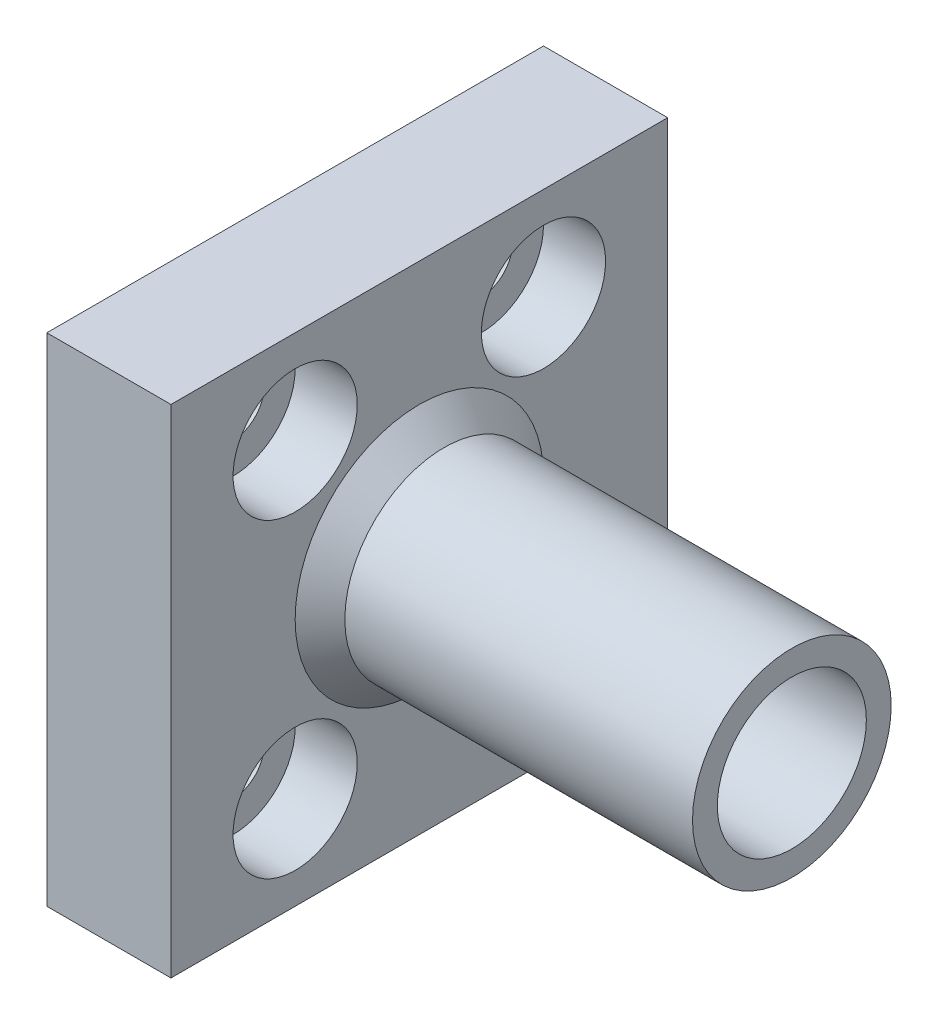
SolidWorks part; units mm, degrees
ref_plane "Front Plane" through (0, 0, 0) normal (0, 0, 1) x (1, 0, 0)
ref_plane "Top Plane" through (0, 0, 0) normal (0, 1, 0) x (1, 0, 0)
ref_plane "Right Plane" through (0, 0, 0) normal (1, 0, 0) x (0, 0, -1)
other "Configuration Table"
sketch "Sketch1" plane through (0, 0, 0) normal (1, 0, 0) x (0, 0, -1)
  line L1 (20, -20) -> (-20, -20)
  line L2 (20, -20) -> (20, 20)
  line L3 (20, 20) -> (-20, 20)
  line L4 (-20, -20) -> (-20, 20)
  line L5 (20, -20) -> (-20, 20) construction
  line L6 (20, 20) -> (-20, -20) construction
  point P0 (0, 0)
  dimension "D1" = 40
  dimension "D2" = 40
extrude "Boss-Extrude1" add sketch "Sketch1" along normal blind 10
sketch "Sketch2" plane through (10, 0, 0) normal (1, 0, 0) x (0, 0, -1)
  circle A0 centre (0, 0) radius 8
extrude "Boss-Extrude2" add sketch "Sketch2" along normal blind 30
sketch "Sketch3" plane through (10, 0, 0) normal (1, 0, 0) x (0, 0, -1)
  line L0 (-10, -20) -> (-10, 20) construction
  line L1 (-20, -20) -> (20, -20) construction
  line L2 (20, 20) -> (-20, 20) construction
  line L3 (10, -20) -> (10, 20) construction
  dimension "D1" = 10
  dimension "D2" = 10
sketch "Sketch4" plane through (10, 0, 0) normal (1, 0, 0) x (0, 0, -1)
  line L0 (-10, -20) -> (-10, 20) construction
  line L1 (10, -20) -> (10, 20) construction
  circle A0 centre (-10, 12.5) radius 2.5
  circle A1 centre (-10, -12.5) radius 2.5
  circle A2 centre (10, 12.5) radius 2.5
  circle A3 centre (10, -12.5) radius 2.5
  dimension "D1" = 12.5
  dimension "D2" = 12.5
extrude "Cut-Extrude1" cut sketch "Sketch4" against normal through all
sketch "Sketch5" plane through (40, 0, 0) normal (1, 0, 0) x (0, 0, -1)
  circle A0 centre (0, 0) radius 6
extrude "Cut-Extrude2" cut sketch "Sketch5" against normal blind 34
sketch "Sketch6" plane through (10, 0, 0) normal (1, 0, 0) x (0, 0, -1)
  circle A0 centre (-10, 12.5) radius 5
  circle A1 centre (10, 12.5) radius 5
  circle A2 centre (10, -12.5) radius 5
  circle A3 centre (-10, -12.5) radius 5
extrude "Cut-Extrude3" cut sketch "Sketch6" against normal blind 5
sketch "Sketch7" plane through (6, 0, 0) normal (1, 0, 0) x (0, 0, -1)
  circle A0 centre (0, 0) radius 1
extrude "Cut-Extrude4" cut sketch "Sketch7" against normal through all
sketch "Sketch8" plane through (0, 0, 0) normal (-1, 0, 0) x (0, 0, 1)
  circle A0 centre (0, 0) radius 2.5
extrude "Cut-Extrude5" cut sketch "Sketch8" against normal blind 3
chamfer "Chamfer1" distance 2 angle 45 1 edges at (10, 0, -8)
